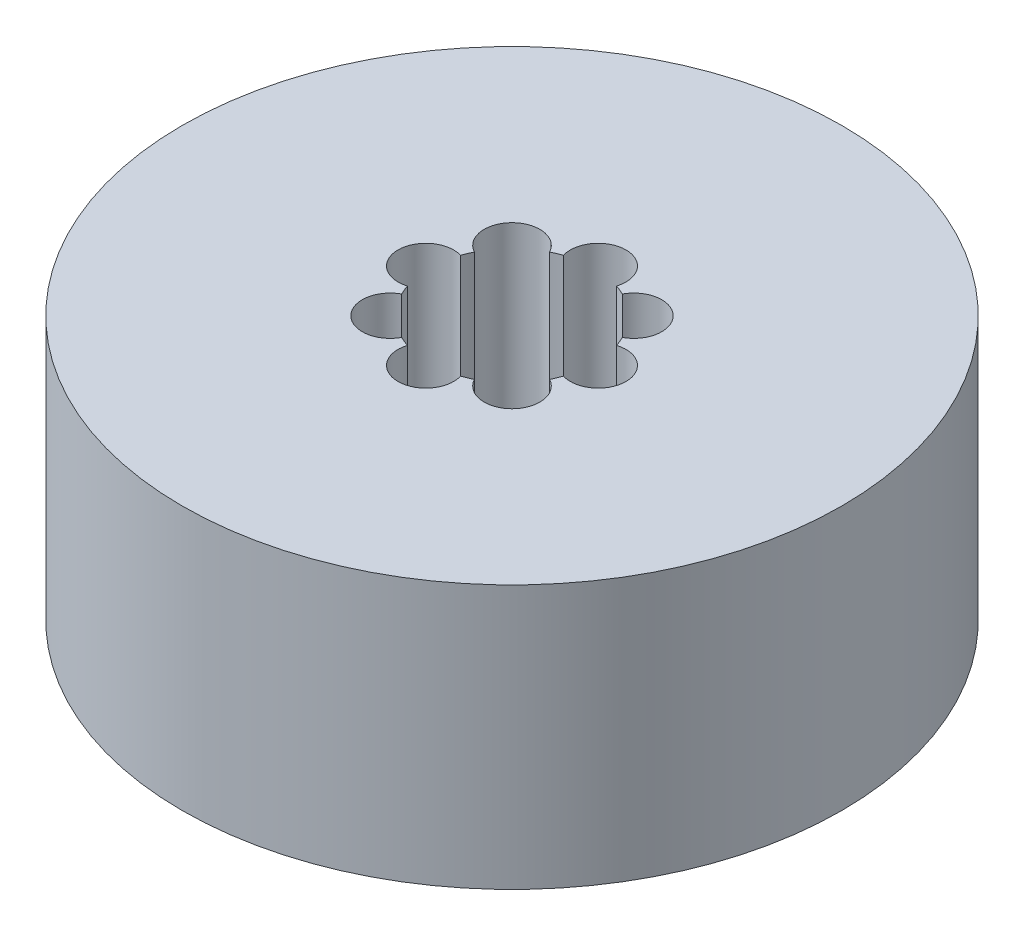
SolidWorks part; units mm, degrees
ref_plane "Front Plane" through (0, 0, 0) normal (0, 0, 1) x (1, 0, 0)
ref_plane "Top Plane" through (0, 0, 0) normal (0, 1, 0) x (1, 0, 0)
ref_plane "Right Plane" through (0, 0, 0) normal (1, 0, 0) x (0, 0, -1)
sketch "Sketch1" plane through (0, 0, 0) normal (0, 1, 0) x (1, 0, 0)
  circle A0 centre (0, 0) radius 20
  dimension "FLANGE_OD" = 40
extrude "Boss-Extrude1" add sketch "Sketch1" along normal blind 16
sketch "Sketch2" plane through (0, 0, 0) normal (0, 1, 0) x (1, 0, 0)
  circle A0 centre (0, 0) radius 5
  dimension "BORE_D" = 10
extrude "Cut-Extrude1" cut sketch "Sketch2" along normal through all
sketch "Sketch3" plane through (0, 16, 0) normal (0, 1, 0) x (1, 0, 0)
  circle A0 centre (0, 0) radius 5.2281 construction
  circle A1 centre (-5.2281, 0) radius 1.687
  dimension "BOLT_D" = 3.374
  dimension "BOLT_PCD" = 10.4563
extrude "Cut-Extrude2" cut sketch "Sketch3" against normal blind 12.358
pattern_circular "CirPattern1" count 8 over 360 about axis through (0, 0, 0) along (0, 1, 0) of "Cut-Extrude2"
